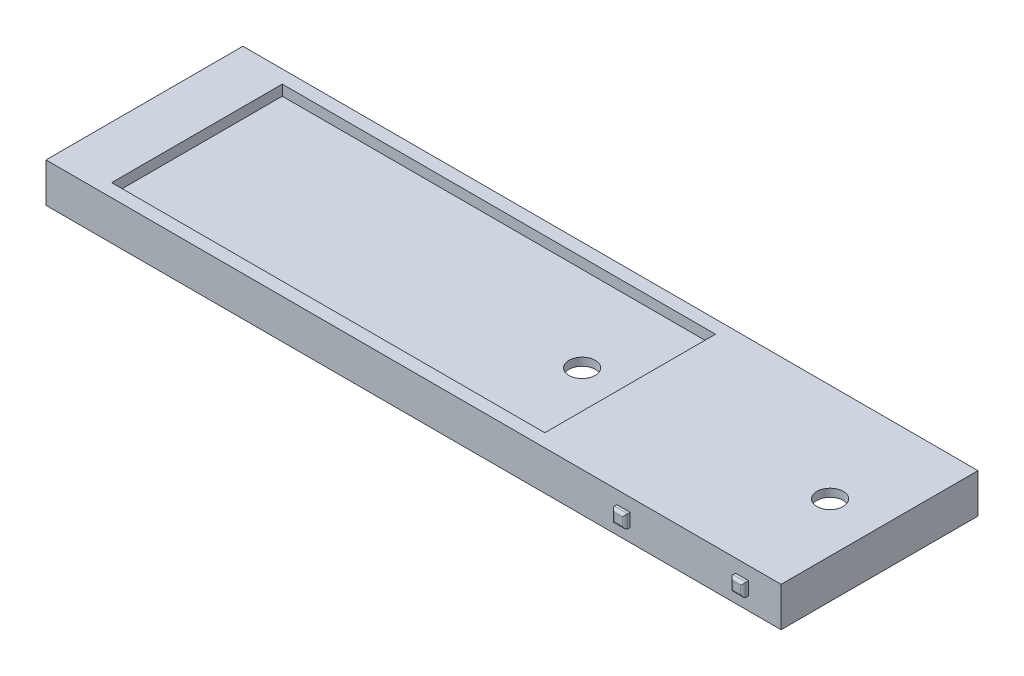
SolidWorks part; units mm, degrees
ref_plane "Front Plane" through (0, 0, 0) normal (0, 0, 1) x (1, 0, 0)
ref_plane "Top Plane" through (0, 0, 0) normal (0, 1, 0) x (1, 0, 0)
ref_plane "Right Plane" through (0, 0, 0) normal (1, 0, 0) x (0, 0, -1)
sketch "Sketch1" plane through (0, 0, 0) normal (0, 1, 0) x (1, 0, 0)
  line L1 (-140, 37.5) -> (140, 37.5)
  line L2 (-140, 37.5) -> (-140, -37.5)
  line L3 (-140, -37.5) -> (140, -37.5)
  line L4 (140, 37.5) -> (140, -37.5)
  line L5 (-140, 37.5) -> (140, -37.5) construction
  line L6 (-140, -37.5) -> (140, 37.5) construction
  point P0 (0, 0)
  dimension "D1" = 280
  dimension "D2" = 75
extrude "Boss-Extrude1" add sketch "Sketch1" along normal blind 15
sketch "Sketch8" plane through (0, 15, 0) normal (0, 1, 0) x (1, 0, 0)
  circle A0 centre (121.1662, 0) radius 5
extrude "Cut-Extrude4" cut sketch "Sketch8" against normal through all
sketch "Sketch10" plane through (0, 15, 0) normal (0, 1, 0) x (1, 0, 0)
  circle A0 centre (26.6983, 0) radius 5
extrude "Cut-Extrude6" cut sketch "Sketch10" against normal through all
sketch "Sketch9" plane through (0, 15, 0) normal (0, 1, 0) x (1, 0, 0)
  line L0 (-140, 37.5) -> (-140, -37.5) construction
  line L1 (-120, 32.5) -> (45, 32.5)
  line L2 (-120, 32.5) -> (-120, -32.5)
  line L3 (-120, -32.5) -> (45, -32.5)
  line L4 (45, 32.5) -> (45, -32.5)
  point P4 (45, 0)
  dimension "D1" = 165
  dimension "D2" = 65
  dimension "D3" = 0
  dimension "D4" = 20
extrude "Cut-Extrude5" cut sketch "Sketch9" against normal blind 4
shell "Shell2" thickness 3 removed face at (-140, 7.5, 0) removed face at (26.6983, 0, 5) removed face at (26.6983, 0, 5) removed face at (121.1662, 0, 5)
sketch "Sketch11" plane through (0, 0, 37.5) normal (0, 0, 1) x (1, 0, 0)
  line L0 (140, 24.9085) -> (65, 24.9085) construction
  line L1 (140, 15) -> (140, 0) construction
  line L2 (-140, 0) -> (140, 0) construction
  line L3 (-140, 15) -> (140, 15) construction
  line L4 (77.5, 10) -> (82.5, 10)
  line L5 (77.5, 10) -> (77.5, 5)
  line L6 (77.5, 5) -> (82.5, 5)
  line L7 (82.5, 10) -> (82.5, 5)
  line L8 (77.5, 10) -> (82.5, 5) construction
  line L9 (77.5, 5) -> (82.5, 10) construction
  line L11 (122.624, 10) -> (127.624, 10)
  line L12 (122.624, 10) -> (122.624, 5)
  line L13 (122.624, 5) -> (127.624, 5)
  line L14 (127.624, 10) -> (127.624, 5)
  line L15 (122.624, 10) -> (127.624, 5) construction
  line L16 (122.624, 5) -> (127.624, 10) construction
  point P4 (125, 0)
  point P5 (80, 0)
  point P8 (80, 7.5)
  point P15 (125.124, 7.5)
  dimension "D1" = 0
  dimension "D3" = 15
  dimension "D4" = 15
  dimension "D5" = 5
  dimension "D6" = 5
  dimension "D7" = 5
  dimension "D8" = 5
  dimension "D9" = 5
extrude "Boss-Extrude4" add sketch "Sketch11" along normal blind 2
fillet "Fillet1" radius 1 8 edges at (125.124, 5, 39.5) (122.624, 7.5, 39.5) (125.124, 10, 39.5) (127.624, 7.5, 39.5) (80, 5, 39.5) (77.5, 7.5, 39.5) (80, 10, 39.5) (82.5, 7.5, 39.5)
